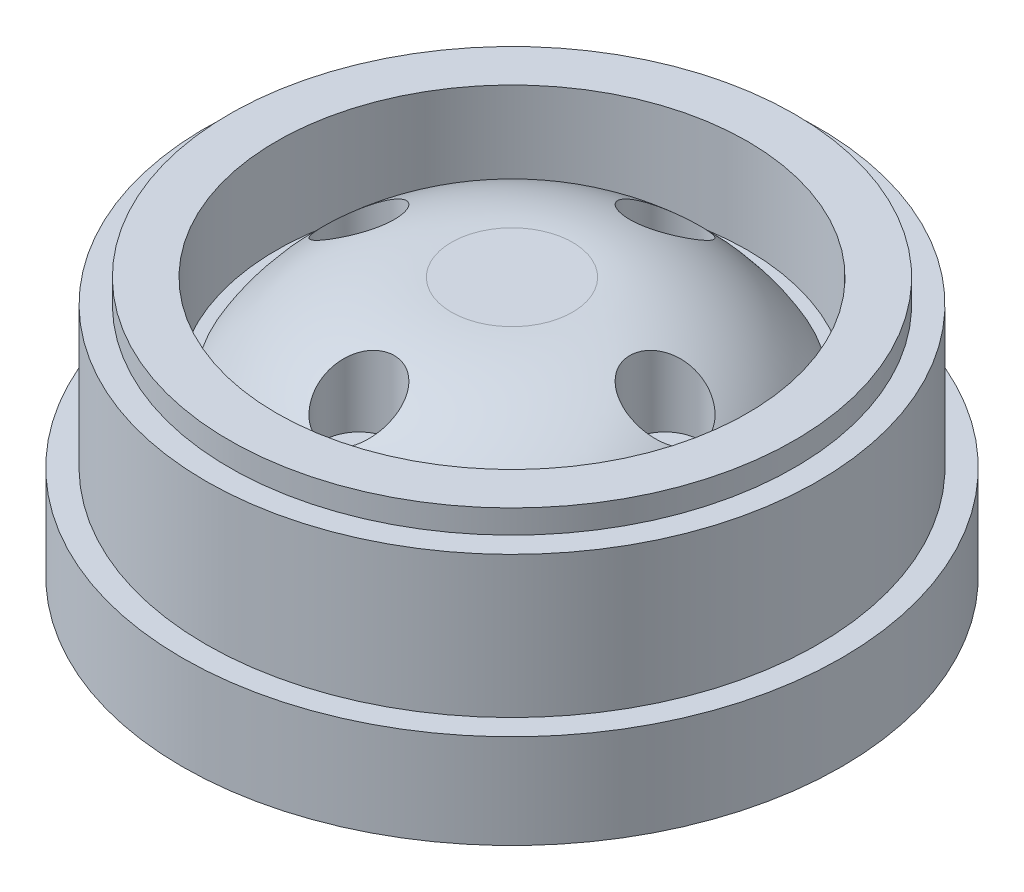
SolidWorks part; units mm, degrees
ref_plane "Front Plane" through (0, 0, 0) normal (0, 0, 1) x (1, 0, 0)
ref_plane "Top Plane" through (0, 0, 0) normal (0, 1, 0) x (1, 0, 0)
ref_plane "Right Plane" through (0, 0, 0) normal (1, 0, 0) x (0, 0, -1)
sketch "Sketch1" plane through (0, 0, 0) normal (0, 1, 0) x (1, 0, 0)
  circle A0 centre (0, 0) radius 14
  dimension "D1" = 28
extrude "Boss-Extrude1" add sketch "Sketch1" along normal blind 4
sketch "Sketch2" plane through (0, 4, 0) normal (0, 1, 0) x (1, 0, 0)
  circle A0 centre (0, 0) radius 13
  circle A1 centre (0, 0) radius 12
  circle A2 centre (0, 0) radius 10
  dimension "D1" = 26
  dimension "D2" = 24
  dimension "D3" = 20
extrude "Boss-Extrude2" add sketch "Sketch2" along normal blind 6 contours A0 A1 region at (-12.6323, 4, 0)
extrude "Boss-Extrude3" add sketch "Sketch2<3>" along normal blind 7 contours A1 A2 region at (-11.6606, 4, 0)
sketch "Sketch2<3>" plane through (0, 4, 0) normal (0, 1, 0) x (1, 0, 0) same geometry as "Sketch2"
extrude "Boss-Extrude4" add sketch "Sketch2<4>" along normal blind 3 contours A2 region at (0, 4, 0)
sketch "Sketch2<4>" plane through (0, 4, 0) normal (0, 1, 0) x (1, 0, 0) same geometry as "Sketch2"
sketch "Sketch3" plane through (0, 7, 0) normal (0, 1, 0) x (1, 0, 0)
  circle A0 centre (0, 0) radius 9.5
  dimension "D1" = 19
extrude "Boss-Extrude5" add sketch "Sketch3" along normal up to surface (4 mm away) up to face at (0, 11, 10)
fillet "Fillet1" radius 8 1 edges at (0, 11, 9.5)
sketch "Sketch5" plane through (0, 11, 0) normal (0, 1, 0) x (1, 0, 0)
  line L0 (0, 0) -> (0, 12.3705) construction
  circle A0 centre (0, 6.5) radius 1.5
  circle A1 centre (6.5, 0) radius 1.5
  circle A2 centre (0, -6.5) radius 1.5
  circle A3 centre (-6.5, 0) radius 1.5
  point P14 (0, 0)
  dimension "D2" = 3
  dimension "D1" = 6.5
  dimension "D3" = 4
extrude "Cut-Extrude1" cut sketch "Sketch5" against normal blind 3.5
sketch "Sketch6" plane through (0, 0, 0) normal (0, -1, 0) x (1, 0, 0)
  circle A0 centre (0, 0) radius 5.1
  dimension "D1" = 10.2
extrude "Cut-Extrude2" cut sketch "Sketch6" against normal blind 4.2
